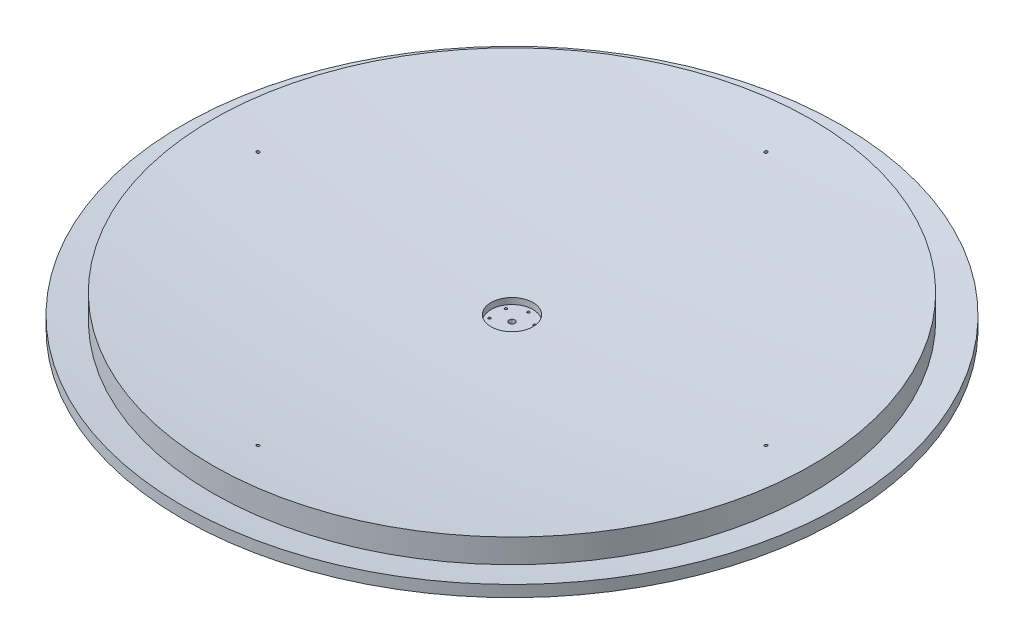
SolidWorks part; units mm, degrees
material "1060 Сплав"
ref_plane "Спереди" through (0, 0, 0) normal (0, 0, 1) x (1, 0, 0)
ref_plane "Сверху" through (0, 0, 0) normal (0, 1, 0) x (1, 0, 0)
ref_plane "Справа" through (0, 0, 0) normal (1, 0, 0) x (0, 0, -1)
sketch "Эскиз1" plane through (0, 0, 0) normal (1, 0, 0) x (0, 0, -1)
  line L0 (0, -21.8058) -> (0, 37.9117) construction
  line L1 (5, 0) -> (550, 0)
  line L4 (34.9997, 10) -> (5, 10)
  line L5 (34.9997, 20.2128) -> (34.9997, 10)
  line L6 (5, 10) -> (5, 0)
  line L7 (500, 12.3006) -> (500, 52.3006)
  line L8 (550, 19.0731) -> (550, 0)
  spline S0 degree 2 poles (-11.5003, 20.0723) (267.366, 19.2423) (546.2327, 58.5399) knots 0 0 0 1 1 1 construction
  spline S1 degree 2 poles (34.9997, 20.2128) (267.4997, 22.3102) (500, 52.3006) knots 0.083373 0.083373 0.083373 0.917106 0.917106 0.917106
  spline S2 degree 2 poles (495, 11.6588) (524.9976, 15.4898) (554.9952, 19.7851) knots 0 0 0 1 1 1 construction
  spline S3 degree 2 poles (500, 12.3006) (525, 15.5256) (550, 19.0731) knots 0.08334 0.08334 0.08334 0.91674 0.91674 0.91674
  spline S4 degree 2 poles (-3.5, 19.9961) (17.5, 20.01) (38.4995, 20.2515) knots 0 0 0 1 1 1 construction
  spline S5 degree 2 poles (0, 20) (17.5, 20.0274) (34.9997, 20.2128) knots 0.083334 0.083334 0.083334 0.916669 0.916669 0.916669 construction
  dimension "D1" = 5
  dimension "D2" = 40
  dimension "D3" = 0
  dimension "D4" = 0
  dimension "D5" = 10
  dimension "D6" = 34.9997
  dimension "D7" = 500
  dimension "D8" = 10
  dimension "D10" = 50
  dimension "D11" = 90
revolve "Повернуть1" add sketch "Эскиз1" angle 360 about L0
sketch "Отверстия под рупор" plane through (0, 10, 0) normal (0, 1, 0) x (1, 0, 0)
  line L0 (0, 49.5654) -> (0, -63.5242) construction
  line L1 (-23.8157, 13.75) -> (23.8157, -13.75) construction
  line L2 (-23.8157, -13.75) -> (23.8157, 13.75) construction
  line L3 (0, 27.5) -> (0, -24.2052) construction
  circle A0 centre (0, 0) radius 27.5 construction
  point P1 (-23.8157, 13.75)
  point P4 (0, 27.5)
  point P5 (23.8157, 13.75)
  point P6 (23.8157, -13.75)
  point P7 (0, -24.2052)
  point P8 (-23.8157, -13.75)
  point P15 (0, 0)
  point P16 (0, 0)
  dimension "D3" = 55
  dimension "D1" = 60
  dimension "D2" = 60
hole_wizard "Отверстие обработанное метчиком M51" positions "Эскиз3" profile "Эскиз4" tap size "M5" standard "ISO" end condition through all
sketch "Эскиз3" plane through (0, 10, 0) normal (0, 1, 0) x (1, 0, 0)
  circle A0 centre (0, 0) radius 27.5 construction
  point P0 (-23.8157, 13.75)
  point P3 (0, 27.5)
  point P6 (23.8157, 13.75)
  point P9 (23.8157, -13.75)
  point P12 (-0.1863, -27.4994)
  point P16 (-23.8157, -13.75)
sketch "Эскиз4" plane through (-23.8157, 10, -13.75) normal (1, 0, 0) x (0, 0, 1)
  line L0 (0, 0) -> (0, 10)
  line L1 (0, 10) -> (2.1, 10)
  line L2 (2.1, 10) -> (2.1, 0)
  line L5 (2.1, 0) -> (0, 0)
  line L11 (0, -6.35) -> (0, 107.95) construction
  dimension "Диаметр проходного сверла" = 4.2
  dimension "Глубина проходного сверла" = 10
cosmetic thread "Отверстие резьбы1" parameters "D2"=5
cosmetic thread "Отверстие резьбы2" parameters "D2"=5
cosmetic thread "Отверстие резьбы3" parameters "D2"=5
cosmetic thread "Отверстие резьбы4" parameters "D2"=5
cosmetic thread "Отверстие резьбы5" parameters "D2"=5
cosmetic thread "Отверстие резьбы6" parameters "D2"=5
sketch "Отверстия под задник" plane through (0, 0, 0) normal (0, -1, 0) x (1, 0, 0)
  line L0 (40.4594, 0) -> (-49959.5406, 0) construction
  line L1 (-264.5034, 364.0576) -> (264.5034, -364.0576) construction
  line L2 (-427.9754, 139.0576) -> (427.9754, -139.0576) construction
  line L3 (-427.9754, -139.0576) -> (427.9754, 139.0576) construction
  line L4 (-264.5034, -364.0576) -> (264.5034, 364.0576) construction
  line L5 (0, -450) -> (0, 450) construction
  line L6 (0, -200049.5654) -> (0, 200063.5242) construction
  circle A0 centre (0, 0) radius 450 construction
  point P0 (0, 450)
  point P1 (0, -450)
  point P2 (264.5034, -364.0576)
  point P3 (427.9754, -139.0576)
  point P4 (427.9754, 139.0576)
  point P5 (264.5034, 364.0576)
  point P6 (-264.5034, 364.0576)
  point P7 (-427.9754, 139.0576)
  point P8 (-264.5034, -364.0576)
  point P9 (-427.9754, -139.0576)
  point P30 (0, 0)
  point P31 (0, 0)
  dimension "D6" = 900
  dimension "D1" = 36
  dimension "D2" = 0
  dimension "D3" = 36
  dimension "D4" = 36
  dimension "D5" = 36
hole_wizard "Отверстие обработанное метчиком M52" positions "Эскиз6" profile "Эскиз7" tap size "M5" standard "ISO"
sketch "Эскиз6" plane through (0, 0, 0) normal (0, -1, 0) x (-1, 0, 0)
  line L0 (264.5034, 364.0576) -> (-264.5034, -364.0576) construction
  circle A0 centre (0, 0) radius 450 construction
  point P0 (0, -450)
  point P3 (264.5034, -364.0576)
  point P6 (427.9754, -139.0576)
  point P9 (427.9754, 139.0576)
  point P12 (264.5034, 364.0576)
  point P18 (0, 450)
  point P21 (-264.5034, 364.0576)
  point P24 (-427.9754, 139.0576)
  point P27 (-427.9754, -139.0576)
  point P30 (-264.5034, -364.0576)
sketch "Эскиз7" plane through (0, 0, 450) normal (1, 0, 0) x (0, 0, -1)
  line L0 (0, 0) -> (0, 6)
  line L1 (0, 6) -> (2.1, 4.7382)
  line L2 (2.1, 4.7382) -> (2.1, 0)
  line L5 (2.1, 0) -> (0, 0)
  line L10 (0, 6) -> (-2.1, 4.7382) construction
  line L11 (0, -6.35) -> (0, 107.95) construction
  dimension "Диаметр сверла" = 4.2
  dimension "Глубина сверла" = 6
  dimension "Угол заточки сверла" = 118
cosmetic thread "Отверстие резьбы7" parameters "D1"=4.2, "D2"=5
cosmetic thread "Отверстие резьбы8" parameters "D1"=4.2, "D2"=5
cosmetic thread "Отверстие резьбы9" parameters "D1"=4.2, "D2"=5
cosmetic thread "Отверстие резьбы10" parameters "D1"=4.2, "D2"=5
cosmetic thread "Отверстие резьбы11" parameters "D1"=4.2, "D2"=5
cosmetic thread "Отверстие резьбы12" parameters "D1"=4.2, "D2"=5
cosmetic thread "Отверстие резьбы13" parameters "D1"=4.2, "D2"=5
cosmetic thread "Отверстие резьбы14" parameters "D1"=4.2, "D2"=5
cosmetic thread "Отверстие резьбы15" parameters "D1"=4.2, "D2"=5
cosmetic thread "Отверстие резьбы16" parameters "D1"=4.2, "D2"=5
sketch "Отверстия под волновод" plane through (0, 0, 0) normal (0, -1, 0) x (1, 0, 0)
  line L0 (0, -200049.5654) -> (0, 200063.5242) construction
  line L1 (10, 10) -> (-10, 10) construction
  line L2 (-10, 10) -> (-10, -10) construction
  line L3 (-10, -10) -> (10, -10) construction
  line L4 (10, -10) -> (10, 10) construction
  circle A0 centre (0, 0) radius 10 construction
  dimension "D1" = 90
  dimension "D2" = 20
hole_wizard "Отверстие обработанное метчиком M2.51" positions "Эскиз9" profile "Эскиз10" tap size "M2.5" standard "ISO"
sketch "Эскиз9" plane through (0, 0, 0) normal (0, -1, 0) x (-1, 0, 0)
  point P0 (10, -10)
  point P3 (-10, -10)
  point P6 (-10, 10)
  point P9 (10, 10)
sketch "Эскиз10" plane through (-10, 0, 10) normal (1, 0, 0) x (0, 0, -1)
  line L0 (0, 0) -> (0, 5.6159)
  line L1 (0, 5.6159) -> (1.025, 5)
  line L2 (1.025, 5) -> (1.025, 0)
  line L5 (1.025, 0) -> (0, 0)
  line L10 (0, 5.6159) -> (-1.025, 5) construction
  line L11 (0, -6.35) -> (0, 107.95) construction
  dimension "Диаметр сверла" = 2.05
  dimension "Глубина сверла" = 5
  dimension "Угол заточки сверла" = 118
cosmetic thread "Отверстие резьбы17" parameters "D1"=5, "D2"=2.5
cosmetic thread "Отверстие резьбы18" parameters "D1"=5, "D2"=2.5
cosmetic thread "Отверстие резьбы19" parameters "D1"=5, "D2"=2.5
cosmetic thread "Отверстие резьбы20" parameters "D1"=5, "D2"=2.5
sketch "Эскиз11" plane through (0, 0, 0) normal (0, 1, 0) x (1, 0, 0)
  circle A0 centre (0, 0) radius 424 construction
  dimension "D1" = 848
hole_wizard "Отверстие обработанное метчиком M61" positions "Трехмерный эскиз2" profile "Эскиз13" tap size "M6" standard "ISO"
sketch3d "Трехмерный эскиз2"
  line L0 (0, 0, -424) -> (0, 43.2424, -424) construction
  line L1 (0, 0, -450) -> (0, 0, 450) construction
  line L3 (-424, 0, 0) -> (-424, 43.2424, 0) construction
  line L4 (40.4594, 0, 0) -> (-49959.5406, 0, 0) construction
  line L6 (424, 0, 0) -> (424, 43.2424, 0) construction
  line L9 (0, 0, 424) -> (0, 43.2424, 424) construction
  circle A0 centre (0, 0, 0) radius 424 construction
  point P2 (0, 43.2424, -424)
  point P7 (0, 424, 0)
  point P11 (-424, 43.2424, 0)
  point P16 (424, 43.2424, 0)
  point P21 (0, 43.2424, 424)
sketch "Эскиз13" plane through (0, 43.2424, 424) normal (1, 0, 0) x (0, 0.1087, 0.9941)
  line L0 (0, 0) -> (0, 12.5022)
  line L1 (0, 12.5022) -> (2.5, 11)
  line L2 (2.5, 11) -> (2.5, 0)
  line L5 (2.5, 0) -> (0, 0)
  line L10 (0, 12.5022) -> (-2.5, 11) construction
  line L11 (0, -6.35) -> (0, 107.95) construction
  dimension "Диаметр сверла" = 5
  dimension "Глубина сверла" = 11
  dimension "Угол заточки сверла" = 118
cosmetic thread "Отверстие резьбы21" parameters "D1"=11.0008, "D2"=6
cosmetic thread "Отверстие резьбы22" parameters "D1"=11.0008, "D2"=6
cosmetic thread "Отверстие резьбы23" parameters "D1"=11.0008, "D2"=6
cosmetic thread "Отверстие резьбы24" parameters "D1"=11.0008, "D2"=6
